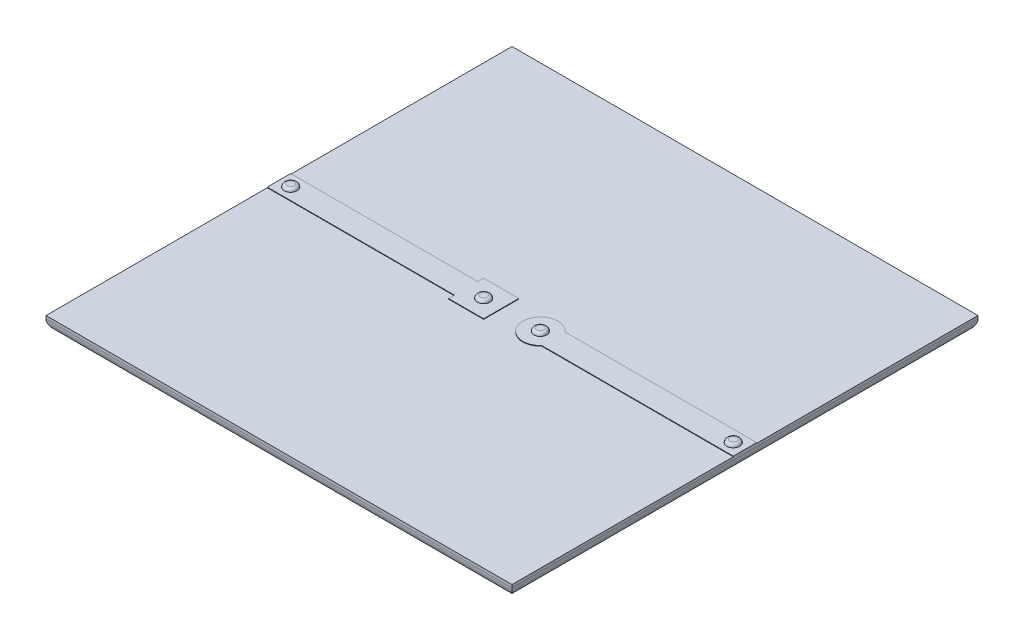
SolidWorks part; units mm, degrees
ref_plane "Спереди" through (0, 0, 0) normal (0, 0, 1) x (1, 0, 0)
ref_plane "Сверху" through (0, 0, 0) normal (0, 1, 0) x (1, 0, 0)
ref_plane "Справа" through (0, 0, 0) normal (1, 0, 0) x (0, 0, -1)
sketch "Эскиз1" plane through (0, 0, 0) normal (0, 1, 0) x (1, 0, 0)
  line L1 (39.85, 39.85) -> (-39.85, 39.85)
  line L2 (39.85, 39.85) -> (39.85, -39.85)
  line L3 (39.85, -39.85) -> (-39.85, -39.85)
  line L4 (-39.85, 39.85) -> (-39.85, -39.85)
  line L5 (39.85, 39.85) -> (-39.85, -39.85) construction
  line L6 (39.85, -39.85) -> (-39.85, 39.85) construction
  point P0 (0, 0)
  dimension "D1" = 79.7
  dimension "D2" = 79.7
extrude "Бобышка-Вытянуть1" add sketch "Эскиз1" against normal blind 2.5
fillet "Скругление1" radius 2 4 edges at (-39.85, -2.5, 0) (0, -2.5, -39.85) (39.85, -2.5, 0) (0, -2.5, 39.85)
sketch "Эскиз2" plane through (0, 0, 0) normal (0, 1, 0) x (1, 0, 0)
  line L0 (39.85, 0) -> (-39.85, 0) construction
  line L1 (39.85, -39.85) -> (39.85, 39.85) construction
  line L2 (-39.85, 39.85) -> (-39.85, -39.85) construction
  line L8 (39.85, -2) -> (2.85, -2)
  line L9 (39.85, -2) -> (39.85, 2)
  line L10 (39.85, 2) -> (2.85, 2)
  line L11 (2.85, -2) -> (2.85, 2)
  line L12 (-2.85, -2) -> (-39.85, -2)
  line L13 (-2.85, -2) -> (-2.85, 2)
  line L14 (-2.85, 2) -> (-39.85, 2)
  line L15 (-39.85, -2) -> (-39.85, 2)
  point P14 (39.85, 0)
  point P15 (-39.85, 0)
  point P16 (-2.85, 0)
  point P17 (2.85, 0)
  point P18 (4.1012, 0)
  point P19 (39.85, 0)
  point P20 (-39.85, 0)
  point P21 (-4.0962, 0)
  dimension "D1" = 37
  dimension "D2" = 37
  dimension "D3" = 4
  dimension "D4" = 4
extrude "Бобышка-Вытянуть2" add sketch "Эскиз2" along normal blind 0.1
sketch "Эскиз3" plane through (0, 0, 0) normal (0, 1, 0) x (1, 0, 0)
  line L0 (-2.85, 0) -> (-4.85, 0) construction
  line L1 (-2.85, -2) -> (-2.85, 2) construction
  line L2 (2.85, 0) -> (4.85, 0) construction
  line L3 (2.85, 2) -> (2.85, -2) construction
  line L5 (-7.85, 3) -> (-1.85, 3)
  line L6 (-7.85, 3) -> (-7.85, -3)
  line L7 (-7.85, -3) -> (-1.85, -3)
  line L8 (-1.85, 3) -> (-1.85, -3)
  line L9 (-7.85, 3) -> (-1.85, -3) construction
  line L10 (-7.85, -3) -> (-1.85, 3) construction
  circle A0 centre (4.85, 0) radius 3
  dimension "D3" = 6
  dimension "D1" = 2
  dimension "D2" = 2
  dimension "D4" = 6
extrude "Бобышка-Вытянуть3" add sketch "Эскиз3" along normal blind 0.1
sketch "Эскиз4" plane through (0, 0.1, 0) normal (0, 1, 0) x (1, 0, 0)
  line L0 (39.85, -2) -> (39.85, 2) construction
  line L1 (-39.85, 2) -> (-39.85, -2) construction
  line L2 (-1.85, -3) -> (-1.85, 3) construction
  line L3 (-7.85, -3) -> (-1.85, -3) construction
  line L4 (-39.85, -2) -> (-7.85, -2) construction
  line L5 (7.0861, -2) -> (39.85, -2) construction
  circle A0 centre (4.85, 0) radius 1.1
  circle A1 centre (-4.85, 0) radius 1.1
  circle A2 centre (37.85, 0) radius 1.1
  circle A3 centre (-37.85, 0) radius 1.1
  arc A5 (7.0861, 2) -> (7.0861, -2) centre (4.85, 0) ccw construction
  dimension "D5" = 2.2
  dimension "D1" = 2
  dimension "D2" = 2
  dimension "D3" = 3
  dimension "D4" = 3
  dimension "D6" = 2
  dimension "D7" = 2
extrude "Бобышка-Вытянуть4" add sketch "Эскиз4" along normal blind 0.5
fillet "Скругление2" radius 0.5 4 edges at (-37.85, 0.6, 1.1) (-4.85, 0.6, 1.1) (4.85, 0.6, 1.1) (37.85, 0.6, 1.1)
